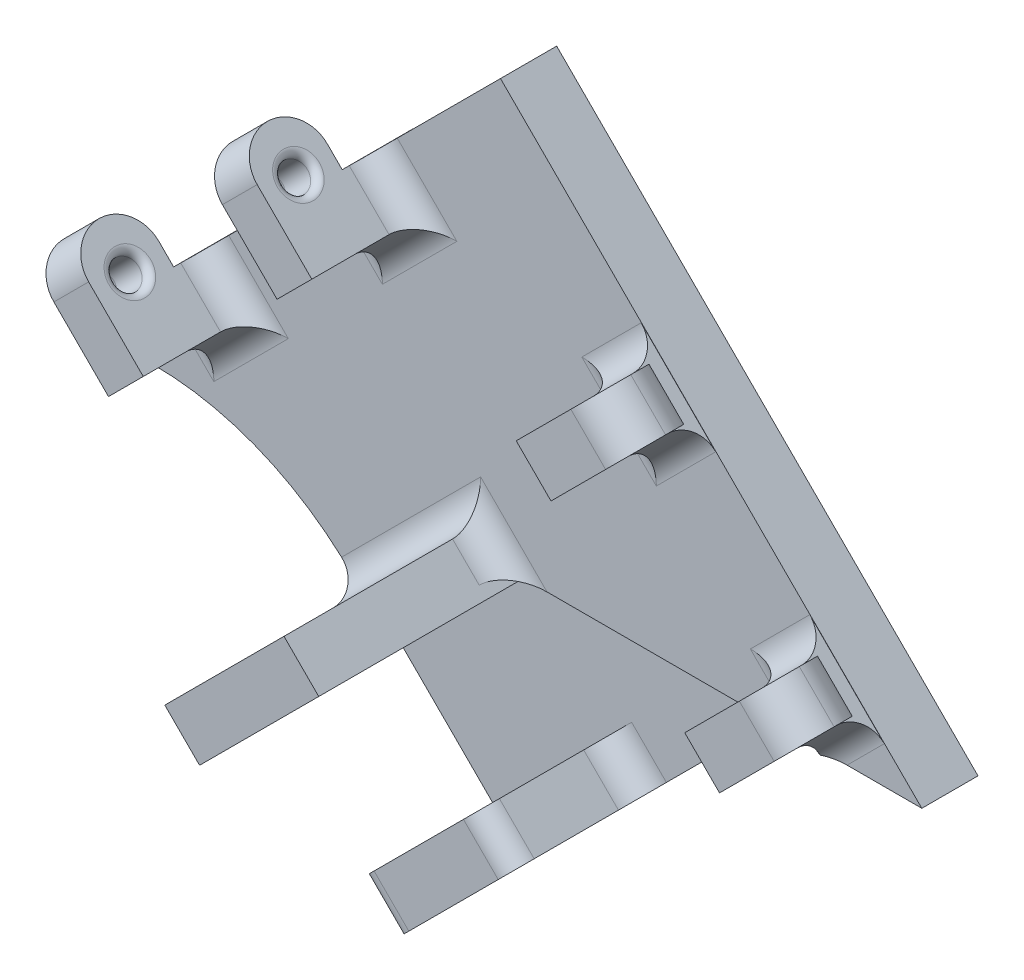
SolidWorks part; units mm, degrees
ref_plane "Front Plane" through (0, 0, 0) normal (0, 0, 1) x (1, 0, 0)
ref_plane "Top Plane" through (0, 0, 0) normal (0, 1, 0) x (1, 0, 0)
ref_plane "Right Plane" through (0, 0, 0) normal (1, 0, 0) x (0, 0, -1)
sketch "Sketch1" plane through (0, 0, 0) normal (0, 0, 1) x (1, 0, 0)
  line L0 (0, 0) -> (30, 0) construction
  line L1 (0, 0) -> (-30, 0) construction
  line L2 (-30, 0) -> (30, 0)
  line L3 (0, 0) -> (0, 35.6261) construction
  line L4 (30, 0) -> (0, 30)
  line L5 (0, 30) -> (-30, 0)
  dimension "D1" = 30
  dimension "D2" = 30
  dimension "D3" = 45
extrude "Boss-Extrude1" add sketch "Sketch1" along normal blind 4
sketch "Sketch2" plane through (0, 0, 4) normal (0, 0, 1) x (1, 0, 0)
  line L0 (0, 30) -> (0, -10) construction
  line L1 (1.4142, -17.8995) -> (-9.8995, -6.5858)
  line L2 (0, 0) -> (15, 15) construction
  line L3 (30, 0) -> (0, 30) construction
  line L4 (0, 0) -> (-15, 15) construction
  line L5 (0, 30) -> (-30, 0) construction
  line L6 (1.4142, -17.8995) -> (9.8995, -9.4142)
  line L7 (-9.8995, -6.5858) -> (-1.4142, 1.8995)
  line L8 (9.8995, -9.4142) -> (-1.4142, 1.8995)
  line L9 (1.4142, -17.8995) -> (-1.4142, 1.8995) construction
  line L10 (-9.8995, -6.5858) -> (9.8995, -9.4142) construction
  line L12 (-30, 0) -> (30, 0) construction
  point P4 (0, -6)
  point P13 (0, -8)
  point P15 (0, 1.305)
  dimension "D1" = 90
  dimension "D2" = 16
  dimension "D3" = 12
  dimension "D4" = 0
  dimension "D5" = 8
extrude "Boss-Extrude2" add sketch "Sketch2" along normal blind 13 from offset 4 offset against normal yes
sketch "Sketch5" plane through (0, 0, 4) normal (0, 0, 1) x (1, 0, 0)
  line L0 (-10, 20) -> (10, 20) construction
  line L1 (0, 30) -> (-30, 0) construction
  line L2 (30, 0) -> (0, 30) construction
  line L3 (-22, 8) -> (22, 8) construction
  line L4 (-10, 20) -> (-13.5355, 23.5355) construction
  line L5 (-22, 8) -> (-25.5355, 11.5355) construction
  line L6 (12.687, 17.313) -> (16.2225, 20.8485) construction
  line L7 (24.687, 5.313) -> (28.2225, 8.8485) construction
  line L8 (-8.409, 15.9341) -> (-14.0659, 21.591)
  line L9 (-8.409, 15.9341) -> (-5.9341, 18.409)
  line L10 (-14.0659, 21.591) -> (-11.591, 24.0659)
  line L11 (-5.9341, 18.409) -> (-11.591, 24.0659)
  line L12 (-8.409, 15.9341) -> (-11.591, 24.0659) construction
  line L13 (-14.0659, 21.591) -> (-5.9341, 18.409) construction
  line L14 (-20.409, 3.9341) -> (-26.0659, 9.591)
  line L15 (-20.409, 3.9341) -> (-17.9341, 6.409)
  line L16 (-26.0659, 9.591) -> (-23.591, 12.0659)
  line L17 (-17.9341, 6.409) -> (-23.591, 12.0659)
  line L18 (-20.409, 3.9341) -> (-23.591, 12.0659) construction
  line L19 (-26.0659, 9.591) -> (-17.9341, 6.409) construction
  line L20 (22, 8) -> (25.5355, 11.5355) construction
  line L21 (10, 20) -> (13.5355, 23.5355) construction
  line L22 (8.6211, 15.722) -> (14.278, 21.3789)
  line L23 (8.6211, 15.722) -> (11.096, 13.2471)
  line L24 (14.278, 21.3789) -> (16.7529, 18.904)
  line L25 (11.096, 13.2471) -> (16.7529, 18.904)
  line L26 (8.6211, 15.722) -> (16.7529, 18.904) construction
  line L27 (14.278, 21.3789) -> (11.096, 13.2471) construction
  line L28 (20.6211, 3.722) -> (26.278, 9.3789)
  line L29 (20.6211, 3.722) -> (23.096, 1.2471)
  line L30 (26.278, 9.3789) -> (28.7529, 6.904)
  line L31 (23.096, 1.2471) -> (28.7529, 6.904)
  line L33 (-30, 0) -> (-3.3137, 0) construction
  line L34 (20.6211, 3.722) -> (28.7529, 6.904) construction
  line L35 (26.278, 9.3789) -> (23.096, 1.2471) construction
  line L36 (-30, 0) -> (-3.3137, 0) construction
  dimension "D1" = 3.5
  dimension "D2" = 90
  dimension "D3" = 8
  dimension "D4" = 3.5
  dimension "D5" = 90
  dimension "D6" = 3.8
  dimension "D7" = 3.8
  dimension "D8" = 3.5
  dimension "D9" = 3.5
  dimension "D10" = 20
  dimension "D11" = 8
  dimension "D12" = 90
  dimension "D13" = 90
  dimension "D14" = 90
  dimension "D15" = 8
  dimension "D16" = 90
extrude "Boss-Extrude3" add sketch "Sketch5" along normal blind 5 from offset 2.5
sketch "Sketch6" plane through (10.9244, -10.9244, 0) normal (0.7071, -0.7071, 0) x (0.7071, 0.7071, 0)
  line L1 (17.2132, 6.5) -> (25.2132, 6.5) construction
  line L2 (21.2132, 4) -> (21.2132, 0) construction
  circle A0 centre (22.0982, 9) radius 1
  dimension "D1" = 2.5
  dimension "D2" = 0.885
sketch "Sketch7" plane through (-8.2374, -8.2374, 0) normal (-0.7071, -0.7071, 0) x (0, 0, 1)
  line L0 (4, 21.2132) -> (0, 21.2132) construction
  line L1 (11.5, 25.2132) -> (11.5, 17.2132) construction
  circle A0 centre (9, 22.0982) radius 1
  dimension "D1" = 0.885
  dimension "D2" = 2.5
sketch "Sketch8" plane through (0, 0, 11.5) normal (0, 0, 1) x (1, 0, 0)
  line L0 (-20.409, 3.9341) -> (-17.9341, 6.409)
  line L1 (-20.409, 3.9341) -> (-23.2472, 6.7723)
  line L2 (-17.9341, 6.409) -> (-20.7723, 9.2472)
  line L3 (-23.2472, 6.7723) -> (-20.7723, 9.2472)
  line L4 (-8.409, 15.9341) -> (-5.9341, 18.409)
  line L5 (-8.409, 15.9341) -> (-11.245, 18.7701)
  line L6 (-5.9341, 18.409) -> (-8.7701, 21.245)
  line L7 (-11.245, 18.7701) -> (-8.7701, 21.245)
  line L8 (8.6211, 15.722) -> (11.096, 13.2471)
  line L9 (8.6211, 15.722) -> (11.4337, 18.5345)
  line L10 (11.096, 13.2471) -> (13.9086, 16.0597)
  line L11 (11.4337, 18.5345) -> (13.9086, 16.0597)
  line L12 (8.6211, 15.722) -> (11.096, 13.2471) construction
  line L14 (23.096, 1.2471) -> (20.6211, 3.722)
  line L15 (23.096, 1.2471) -> (25.9085, 4.0597)
  line L16 (20.6211, 3.722) -> (23.4337, 6.5345)
  line L17 (25.9085, 4.0597) -> (23.4337, 6.5345)
extrude "Boss-Extrude4" add sketch "Sketch8" against normal blind 10
extrude "Cut-Extrude5" cut sketch "Sketch6" against normal blind 25
extrude "Cut-Extrude6" cut sketch "Sketch7" against normal blind 25
fillet "Fillet2" radius 2.5 8 edges at (15.5154, 20.1414, 11.5) (15.5154, 20.1414, 6.5) (27.5154, 8.1414, 6.5) (27.5154, 8.1414, 11.5) (-24.8284, 10.8284, 6.5) (-12.8284, 22.8284, 6.5) (-12.8284, 22.8284, 11.5) (-24.8284, 10.8284, 11.5)
sketch "Sketch10" plane through (0, 0, 13) normal (0, 0, 1) x (1, 0, 0)
  line L0 (-7.4246, -9.0607) -> (-1.0607, -15.4246)
  line L1 (-7.4246, -9.0607) -> (1.0607, -0.5754)
  line L2 (-1.0607, -15.4246) -> (7.4246, -6.9393)
  line L3 (1.0607, -0.5754) -> (7.4246, -6.9393)
  line L5 (-9.8995, -6.5858) -> (1.4142, -17.8995) construction
  line L6 (1.4142, -17.8995) -> (9.8995, -9.4142) construction
  dimension "D1" = 12
  dimension "D2" = 9
  dimension "D3" = 0
  dimension "D4" = 3.5
extrude "Cut-Extrude8" cut sketch "Sketch10" against normal blind 9.5
sketch "Sketch11" plane through (9.6569, -9.6569, 0) normal (0.7071, -0.7071, 0) x (0, 0, -1)
  line L0 (-13, -11.6569) -> (-13, 0.3431) construction
  line L2 (-13, -11.6569) -> (0, -11.6569) construction
  circle A0 centre (-9, -5.6569) radius 1
  dimension "D1" = 4
  dimension "D2" = 6
extrude "Cut-Extrude9" cut sketch "Sketch11" against normal blind 20
fillet "Fillet3" radius 20 1 edges at (-3.3137, 0, 2)
sketch "Sketch13" plane through (0, 0, 13) normal (0, 0, 1) x (1, 0, 0)
  line L0 (-1.4142, 1.8995) -> (-9.8995, -6.5858)
  line L1 (-9.8995, -6.5858) -> (-7.4246, -9.0607)
  line L2 (-7.4246, -9.0607) -> (1.0607, -0.5754)
  line L3 (1.0607, -0.5754) -> (-1.4142, 1.8995)
extrude "Boss-Extrude5" add sketch "Sketch13" along normal blind 5
sketch "Sketch14" plane through (0, 0, 3.5) normal (0, 0, 1) x (1, 0, 0)
  line L0 (0.4853, 0) -> (9.8995, -9.4142)
  line L1 (9.8995, -9.4142) -> (19.3137, 0)
  line L2 (0.4853, 0) -> (30, 0) construction
  line L3 (19.3137, 0) -> (0.4853, 0)
extrude "Boss-Extrude6" add sketch "Sketch14" against normal blind 3.5
sketch "Sketch15" plane through (9.6569, -9.6569, 0) normal (0.7071, -0.7071, 0) x (0, 0, -1)
  circle A0 centre (-9, -5.6569) radius 1.9
extrude "Cut-Extrude10" cut sketch "Sketch15" against normal blind 1
fillet "Fillet5" radius 0.5 2 edges at (-3.8891, -5.5251, 9) (-4.9497, -1.636, 9)
fillet "Fillet6" radius 0.5 9 edges at (-23.1561, 6.6812, 9) (-10.0955, 22.5703, 9) (11.3683, 18.4691, 9) (27.2573, 5.4085, 9) (3.8891, -10.4749, 9) (23.3683, 6.4691, 9) (15.2573, 17.4085, 9) (-11.1561, 18.6812, 9) (-22.0955, 10.5703, 9)
fillet "Fillet7" radius 2 15 edges at (22.0274, 5.1283, 4) (21.8586, 2.4846, 4) (24.5023, 2.6534, 4) (10.0274, 17.1283, 4) (9.8586, 14.4846, 4) (12.5023, 14.6534, 4) (-7.3483, 19.8232, 4) (-19.3483, 7.8232, 4) (-7.1716, 17.1716, 4) (-9.8232, 17.3483, 4) (-19.1716, 5.1716, 4) (-21.8232, 5.3483, 4) (8.6621, -8.1768, 3.5) (-0.4645, 0.9497, 4) (-5.6569, -2.3431, 4)
fillet "Fillet8" radius 1.5 2 edges at (8.6621, -8.1768, 13) (0.1768, -16.6621, 13)
